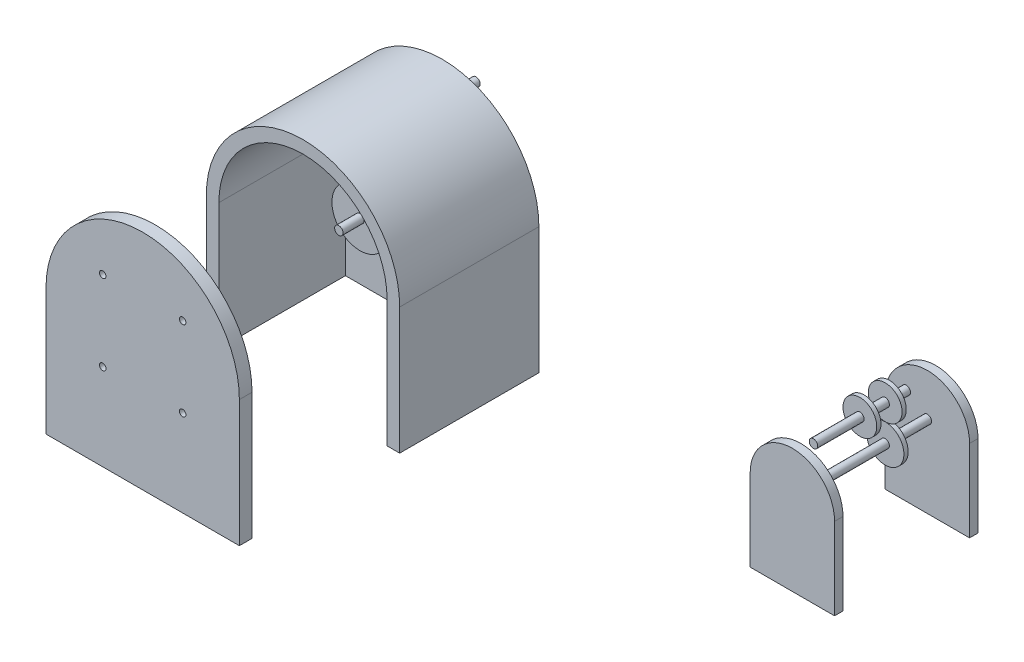
SolidWorks part; units mm, degrees
ref_plane "Front Plane" through (0, 0, 0) normal (0, 0, 1) x (1, 0, 0)
ref_plane "Top Plane" through (0, 0, 0) normal (0, 1, 0) x (1, 0, 0)
ref_plane "Right Plane" through (0, 0, 0) normal (1, 0, 0) x (0, 0, -1)
sketch "Sketch1" plane through (0, 0, 0) normal (0, 0, 1) x (1, 0, 0)
  circle A0 centre (0, 0) radius 10.2407
  circle A1 centre (0, 14.301) radius 4.0604
  circle A2 centre (12.3851, -7.1505) radius 4.0604
  circle A3 centre (-12.3851, -7.1505) radius 4.0604
  circle A4 centre (0, 0) radius 18.3614
  circle A5 centre (0, 0) radius 22.9168
  dimension "D1" = 3
extrude "Boss-Extrude1" add sketch "Sketch1" along normal blind 3 contours A5 A4 | A3 | A0 | A1 | A2 region at (0, 0, 0) region at (0, 14.301, 0) region at (12.3851, -7.1505, 0) region at (-12.3851, -7.1505, 0) region at (-22.2686, 0, 0)
sketch "Sketch2" plane through (0, 0, 0) normal (0, 0, -1) x (-1, 0, 0)
  circle A0 centre (0, 0) radius 1.3984
  circle A1 centre (0, 14.301) radius 1
  circle A2 centre (12.3851, -7.1505) radius 1
  circle A3 centre (-12.3851, -7.1505) radius 1
  dimension "D1" = 3
extrude "Boss-Extrude2" add sketch "Sketch2" along normal blind 8
sketch "Sketch3" plane through (0, 0, 3) normal (0, 0, 1) x (1, 0, 0)
  circle A1 centre (0, 0) radius 22.9168
  circle A2 centre (0, 0) radius 19.942
extrude "Boss-Extrude4" add sketch "Sketch3" along normal blind 30
sketch "Sketch4" plane through (0, 0, 33) normal (0, 0, 1) x (1, 0, 0)
  line L0 (0, 0) -> (22.9168, 0)
  line L1 (0, 0) -> (-22.9168, 0)
  circle A0 centre (0, 0) radius 22.9168 construction
  arc A1 (-22.9168, 0) -> (22.9168, 0) centre (0, 0) ccw
extrude "Cut-Extrude1" cut sketch "Sketch4" against normal blind 30
sketch "Sketch5" plane through (0, 0, 0) normal (0, -1, 0) x (1, 0, 0)
  line L0 (-22.9168, 0) -> (22.9168, 0) construction
  line L1 (-22.9168, 33) -> (-19.942, 33)
  line L2 (-22.9168, 33) -> (-22.9168, 0)
  line L3 (-22.9168, 0) -> (-19.942, 0)
  line L4 (-19.942, 33) -> (-19.942, 0)
  line L6 (19.942, 33) -> (22.9168, 33)
  line L7 (19.942, 33) -> (19.942, 0)
  line L8 (19.942, 0) -> (22.9168, 0)
  line L9 (22.9168, 33) -> (22.9168, 0)
extrude "Boss-Extrude5" add sketch "Sketch5" along normal blind 30
sketch "Sketch6" plane through (0, -30, 0) normal (0, -1, 0) x (1, 0, 0)
  line L0 (22.9168, 0) -> (22.9168, 33) construction
  line L1 (-22.9168, 0) -> (22.9168, 0)
  line L2 (-22.9168, 0) -> (-22.9168, 3)
  line L3 (-22.9168, 3) -> (22.9168, 3)
  line L4 (22.9168, 0) -> (22.9168, 3)
extrude "Boss-Extrude6" add sketch "Sketch6" against normal up to surface (30 mm away) up to face at (0, 11.4584, 16.5)
ref_plane "Plane1" through (0, 0, 18) normal (0, 0, 1) x (1, 0, 0)
sketch "Sketch7" plane through (0, 0, 18) normal (0, 0, 1) x (1, 0, 0)
  circle A0 centre (0, 0) radius 6.6404
extrude "Boss-Extrude8" add sketch "Sketch7" along normal blind 1.5 and the other way blind 1.5 separate body
sketch "Sketch9" plane through (0, 0, 19.5) normal (0, 0, 1) x (1, 0, 0)
  circle A0 centre (0, 0) radius 1
extrude "Boss-Extrude9" add sketch "Sketch9" along normal blind 5
ref_plane "Plane2" through (0, 0, 68) normal (0, 0, 1) x (1, 0, 0)
sketch "Sketch10" plane through (0, 0, 68) normal (0, 0, 1) x (1, 0, 0)
  line L0 (-19.942, -30) -> (19.942, -30)
  line L6 (19.942, 0) -> (19.942, -30)
  line L7 (19.942, -30) -> (22.9168, -30)
  line L8 (22.9168, -30) -> (22.9168, 0)
  line L9 (-22.9168, 0) -> (-22.9168, -30)
  line L10 (-22.9168, -30) -> (-19.942, -30)
  line L11 (-19.942, -30) -> (-19.942, 0)
  line L12 (19.942, 0) -> (19.942, -30)
  line L13 (19.942, -30) -> (22.9168, -30)
  line L14 (22.9168, -30) -> (22.9168, 0)
  line L15 (-22.9168, 0) -> (-22.9168, -30)
  line L16 (-22.9168, -30) -> (-19.942, -30)
  line L17 (-19.942, -30) -> (-19.942, 0)
  arc A2 (19.942, 0) -> (-19.942, 0) centre (0, 0) ccw
  arc A3 (22.9168, 0) -> (-22.9168, 0) centre (0, 0) ccw
  arc A4 (19.942, 0) -> (-19.942, 0) centre (0, 0) ccw
  arc A5 (22.9168, 0) -> (-22.9168, 0) centre (0, 0) ccw
  dimension "D1" = 0
extrude "Boss-Extrude10" add sketch "Sketch10" along normal blind 3 separate body contours L14 A5 L15 L16 L17 A4 L12 L13 | L12 A4 L17 L0 region at (0, -6.9519, 68) region at (-21.4294, -29.2999, 68)
sketch "Sketch11" plane through (0, 0, 71) normal (0, 0, 1) x (1, 0, 0)
  line L0 (0, 0) -> (8.6199, 8.6199) construction
  circle A0 centre (9.471, 9.471) radius 0.7681
  circle A1 centre (9.471, -9.471) radius 0.7681
  circle A2 centre (-9.471, -9.471) radius 0.7681
  circle A3 centre (-9.471, 9.471) radius 0.7681
  dimension "D1" = 4
extrude "Cut-Extrude2" cut sketch "Sketch11" against normal blind 5
ref_plane "Plane3" through (100, 0, 0) normal (1, 0, 0) x (0, 0, -1)
ref_axis "Axis1" through (100, -32.6458, 0) along (0, 1, 0)
ref_axis "Axis2" through (71.0704, 0, 0) along (1, 0, 0)
sketch "Sketch12" plane through (0, 0, 0) normal (0, 0, 1) x (1, 0, 0)
  line L0 (100, -29.1043) -> (100, 29.1043) construction
  line L1 (71.0704, 0) -> (121.4874, 0) construction
  circle A0 centre (100, 0) radius 4
  dimension "D1" = 8
extrude "Boss-Extrude11" add sketch "Sketch12" along normal blind 1 separate body
sketch "Sketch13" plane through (0, 0, 1) normal (0, 0, 1) x (1, 0, 0)
  circle A0 centre (100, 0) radius 1
extrude "Boss-Extrude12" add sketch "Sketch13" along normal blind 11 and the other way blind 11
ref_plane "Plane4" through (0, 0, -5) normal (0, 0, -1) x (-1, 0, 0)
sketch "Sketch14" plane through (0, 0, -5) normal (0, 0, -1) x (-1, 0, 0)
  circle A0 centre (-100, 0) radius 4
extrude "Boss-Extrude13" add sketch "Sketch14" along normal blind 1
sketch "Sketch15" plane through (0, 0, -5) normal (0, 0, -1) x (-1, 0, 0)
  line L0 (-100, 29.1043) -> (-100, -29.1043) construction
  circle A0 centre (-100, -8.4562) radius 4.4389
extrude "Boss-Extrude14" add sketch "Sketch15" along normal blind 1 separate body
sketch "Sketch16" plane through (0, 0, -5) normal (0, 0, 1) x (1, 0, 0)
  circle A0 centre (100, -8.4562) radius 1
extrude "Boss-Extrude15" add sketch "Sketch16" along normal blind 20 and the other way blind 10
sketch "Sketch17" plane through (0, 0, 15) normal (0, 0, 1) x (1, 0, 0)
  line L0 (110, -8.4562) -> (110, -27.8544)
  line L1 (90, -8.4562) -> (90, -27.8544)
  line L2 (90, -27.8544) -> (110, -27.8544)
  circle A0 centre (100, -8.4562) radius 10
  circle M1 centre (100, -8.4562) radius 1
extrude "Boss-Extrude17" add sketch "Sketch17" along normal blind 2 contours M1 | A0 M1 | A0 L1 L2 L0 region at (100, -18.1733, 15) region at (100, -21.8665, 15) region at (100, -8.4562, 15)
mirror "Mirror1" about plane through (0, 0, 0) normal (0, 0, 1) of "Boss-Extrude17"
